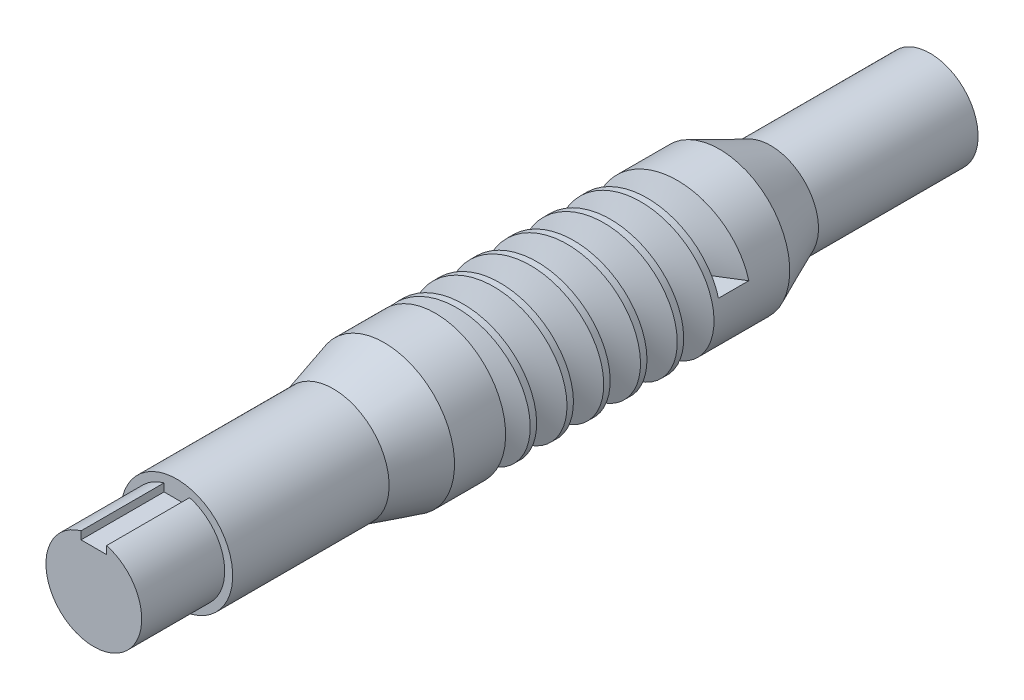
SolidWorks part; units mm, degrees
ref_plane "Alzado" through (0, 0, 0) normal (0, 0, 1) x (1, 0, 0)
ref_plane "Planta" through (0, 0, 0) normal (0, 1, 0) x (1, 0, 0)
ref_plane "Vista lateral" through (0, 0, 0) normal (1, 0, 0) x (0, 0, -1)
sketch "Croquis19" plane through (0, 0, 0) normal (1, 0, 0) x (0, 0, -1)
  line L0 (0, 0) -> (-76.8789, 0) construction
  line L1 (-52.5, 0) -> (-52.5, 22)
  line L2 (-52.5, 22) -> (52.5, 22)
  line L3 (52.5, 22) -> (52.5, 0)
  line L4 (52.5, 0) -> (-52.5, 0)
  point P8 (0, 0)
  dimension "D1" = 105
  dimension "D2" = 44
revolve "Revolución2" add sketch "Croquis19" angle 360 about L0
ref_plane "Plano2" through (0, 0, 36.5) normal (0, 0, 1) x (1, 0, 0)
sketch "Croquis21" plane through (0, 0, 36.5) normal (0, 0, 1) x (1, 0, 0)
  circle A0 centre (0, 0) radius 22 construction
  circle A1 centre (0, 0) radius 22
curve "Hélice/Espiral1" pitch 11.5152 height 76 turns 6.6
sketch "Croquis22" plane through (0, 0, 0) normal (1, 0, 0) x (0, 0, -1)
  line L0 (-41.25, 22) -> (-31.75, 22)
  line L1 (52.5, 22) -> (-52.5, 22) construction
  line L2 (-31.75, 22) -> (-35, 13)
  line L3 (-35, 13) -> (-38, 13)
  line L4 (-38, 13) -> (-41.25, 22)
  line L6 (-36.5, 24.2) -> (-36.5, -24.2) construction
  point P4 (-36.5, 13)
  point P7 (-36.5, 22)
  dimension "D1" = 9.5
  dimension "D2" = 9
  dimension "D3" = 3
sweep "Cortar-Barrer1" cut profiles "Croquis22" path "Hélice/Espiral1" align with end faces yes
sketch "Croquis23" plane through (0, 0, 36.5) normal (0, 0, 1) x (1, 0, 0)
  circle A1 centre (0, 0) radius 22
  circle A2 centre (0, 0) radius 22
  dimension "D1" = 0
extrude "Saliente-Extruir1" add sketch "Croquis23" along normal up to next
sketch "Croquis24" plane through (0, 0, 0) normal (1, 0, 0) x (0, 0, -1)
  line L0 (266.58, 0) -> (-160.1995, 0) construction
  line L1 (-52.5, 22) -> (-68.5, 17.5)
  line L2 (-68.5, 17.5) -> (-117.5, 17.5)
  line L3 (-117.5, 17.5) -> (-117.5, 15)
  line L4 (-117.5, 15) -> (-143.5, 15)
  line L5 (-143.5, 15) -> (-143.5, 0)
  line L6 (-143.5, 0) -> (-52.5, 0)
  line L7 (-52.5, 22) -> (-52.5, -22) construction
  line L8 (-52.5, 0) -> (-52.5, 22)
  line L9 (52.5, -22) -> (52.5, 22) construction
  line L10 (52.5, 0) -> (52.5, 22)
  line L11 (52.5, 22) -> (68.5, 15)
  line L12 (68.5, 15) -> (118.5, 15)
  line L13 (118.5, 15) -> (118.5, 0)
  line L14 (118.5, 0) -> (52.5, 0)
  dimension "D1" = 30
  dimension "D2" = 35
  dimension "D3" = 26
  dimension "D4" = 49
  dimension "D5" = 16
  dimension "D6" = 16
  dimension "D7" = 50
  dimension "D8" = 30
revolve "Revolución3" add sketch "Croquis24" angle 360 about L0
sketch "Croquis25" plane through (0, 0, 143.5) normal (0, 0, 1) x (1, 0, 0)
  line L0 (-4, 14.4568) -> (-4, 12)
  line L1 (-4, 12) -> (4, 12)
  line L2 (4, 12) -> (4, 14.4568)
  circle A0 centre (0, 0) radius 15 construction
  arc A1 (4, 14.4568) -> (-4, 14.4568) centre (0, 0) ccw
  point P2 (0, 12)
  dimension "D1" = 3
  dimension "D2" = 8
extrude "Cortar-Extruir1" cut sketch "Croquis25" against normal blind 26 contours L1 L2 A1 L0
